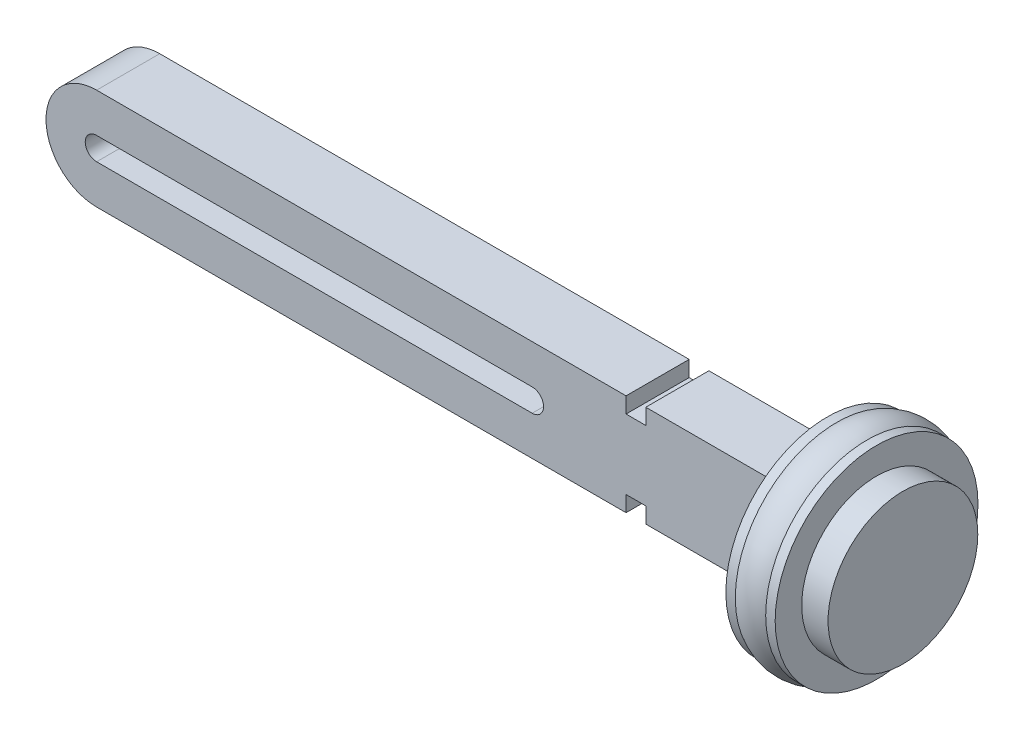
SolidWorks part; units mm, degrees
ref_plane "Front Plane" through (0, 0, 0) normal (0, 0, 1) x (1, 0, 0)
ref_plane "Top Plane" through (0, 0, 0) normal (0, 1, 0) x (1, 0, 0)
ref_plane "Right Plane" through (0, 0, 0) normal (1, 0, 0) x (0, 0, -1)
sketch "Sketch1" plane through (0, 0, 0) normal (0, 0, 1) x (1, 0, 0)
  line L0 (-44.3, 6.415) -> (44.3, 6.415)
  line L6 (44.3, 6.415) -> (44.3, -6.415)
  line L8 (-44.3, -6.415) -> (44.3, -6.415)
  arc A2 (-44.3, 6.415) -> (-44.3, -6.415) centre (-44.3, 0) ccw
  point P1 (0, 6.415)
  point P2 (44.3, 0)
  point P3 (0, 0)
  dimension "D1" = 12.83
  dimension "D2" = 88.6
extrude "Boss-Extrude1" add sketch "Sketch1" along normal blind 8 contours A2 L8 L6 L0
sketch "Sketch2" plane through (44.3, 0, 0) normal (1, 0, 0) x (0, 0, -1)
  line L0 (-8, 6.415) -> (0, 6.415) construction
  circle A0 centre (-4, 0) radius 12.855
  point P4 (-4, 6.415)
  dimension "D1" = 25.71
extrude "Boss-Extrude2" add sketch "Sketch2" along normal blind 6.25 contours A0
sketch "Sketch3" plane through (50.55, 0, 0) normal (1, 0, 0) x (0, 0, -1)
  circle A0 centre (-4, 0) radius 9.49
  circle A1 centre (-4, 0) radius 12.855 construction
  dimension "D1" = 18.98
extrude "Boss-Extrude3" add sketch "Sketch3" along normal blind 3.34
sketch "Sketch4" plane through (0, 0, 0) normal (0, 1, 0) x (1, 0, 0)
  line L0 (45.5, 8.855) -> (49.35, 8.855)
  line L1 (50.55, 8.855) -> (44.3, 8.855) construction
  line L2 (50.55, -16.855) -> (50.55, 8.855) construction
  line L3 (37.822, -4) -> (62.9838, -4) construction
  line L4 (-44.3, 0) -> (44.3, 0) construction
  arc A0 (45.5, 8.855) -> (49.35, 8.855) centre (47.425, 5.3703) cw
  point P5 (47.425, 9.3513)
  point P6 (47.425, 8.855)
  dimension "D1" = 3.9811
  dimension "D2" = 1.2
  dimension "D3" = 1.2
  dimension "D4" = 4
revolve "Revolve1" add sketch "Sketch4" angle 360 about L3
sketch "Sketch5" plane through (0, 0, 8) normal (0, 0, 1) x (1, 0, 0)
  line L0 (-44.3, 0) -> (10.9, 0) construction
  line L1 (-44.3, 1.445) -> (10.9, 1.445)
  line L2 (-44.3, -1.445) -> (10.9, -1.445)
  line L3 (-44.3, 6.415) -> (44.3, 6.415) construction
  arc A0 (-44.3, 1.445) -> (-44.3, -1.445) centre (-44.3, 0) ccw
  arc A1 (10.9, -1.445) -> (10.9, 1.445) centre (10.9, 0) ccw
  point P3 (-16.7, 0)
  point P10 (0, 0)
  point P11 (0, 0)
  point P12 (0, 0)
  point P15 (0, 0)
  dimension "D2" = 55.2
  dimension "D3" = 1.445
  dimension "D1" = 4.97
extrude "Cut-Extrude1" cut sketch "Sketch5" against normal blind 43.34
sketch "Sketch6" plane through (0, 0, 8) normal (0, 0, 1) x (1, 0, 0)
  line L0 (25.3, 6.415) -> (25.3, 4.415)
  line L1 (-44.3, 6.415) -> (44.3, 6.415) construction
  line L2 (25.3, 4.415) -> (22.8, 4.415)
  line L3 (22.8, 4.415) -> (22.8, 6.415)
  line L4 (22.8, 6.415) -> (25.3, 6.415)
  line L5 (44.3, 12.855) -> (44.3, -12.855) construction
  line L6 (25.6781, 0) -> (34.3314, 0) construction
  line L7 (25.3, -4.415) -> (22.8, -4.415)
  line L8 (25.3, -6.415) -> (25.3, -4.415)
  line L9 (22.8, -6.415) -> (25.3, -6.415)
  line L10 (22.8, -4.415) -> (22.8, -6.415)
  dimension "D1" = 19
  dimension "D2" = 2.5
  dimension "D3" = 2
extrude "Cut-Extrude2" cut sketch "Sketch6" against normal blind 53.34
